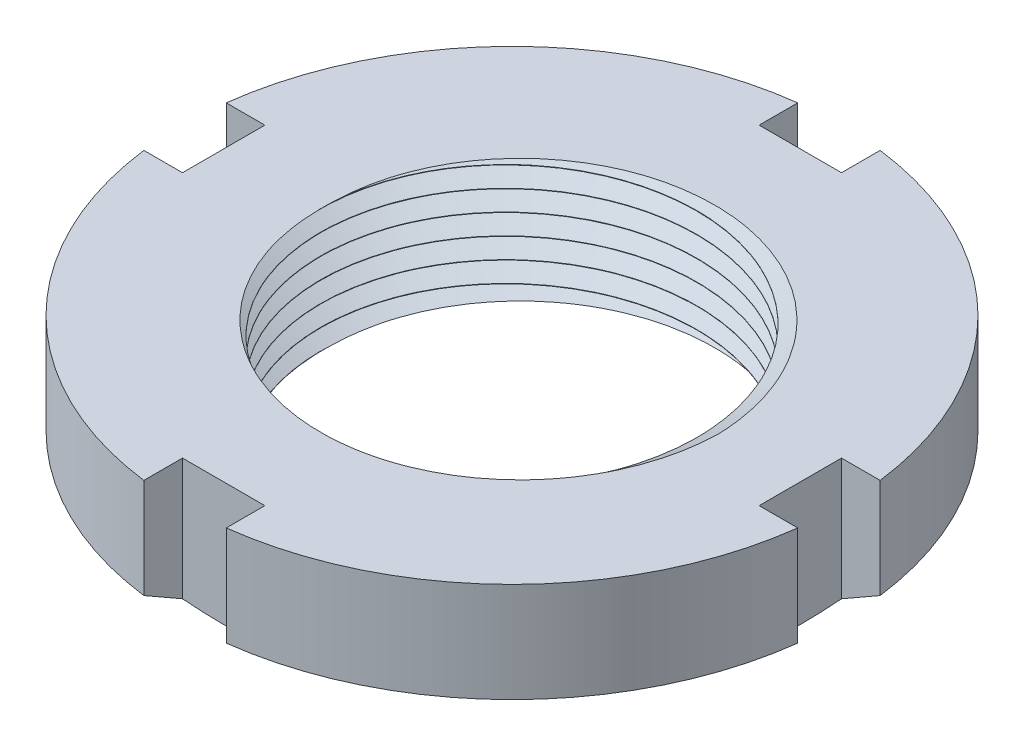
SolidWorks part; units mm, degrees
revolve "Base" add sketch "Esquisse1" angle 360 about L2
sketch "Esquisse1" plane through (0, 0, 0) normal (0, 0, 1) x (1, 0, 0)
  line L1 (9.134, 6) -> (16, 6)
  line L2 (0, 0) -> (0, 1.3) construction
  line L3 (16, 6) -> (16, 1.1547)
  line L4 (14, 0) -> (16, 1.1547)
  line L5 (14, 0) -> (9.134, 0)
  line L6 (-10, 0) -> (10, 0) construction
  line L7 (9.134, 0) -> (9.134, 6)
  line L8 (-16, 0) -> (16, 0) construction
  dimension "Hauteur" = 6
  dimension "D4" = 30
  dimension "D3" = 14
  dimension "Diamètre nominal" = 20
  dimension "Diamètre extérieur" = 32
  dimension "D6" = 9.134
  dimension "D1" = 16
ref_plane "Face" through (0, 0, 0) normal (0, 0, 1) x (1, 0, 0)
ref_plane "Dessus" through (0, 0, 0) normal (0, 1, 0) x (1, 0, 0)
ref_plane "Droite" through (0, 0, 0) normal (1, 0, 0) x (0, 0, -1)
ref_axis "Axe1" through (0, 6.8809, 0) along (0, -1, 0)
sketch "Esquisse2" plane through (0, 6, -4) normal (0, -1, 0) x (1, 0, 0)
  line L0 (0, -12) -> (0, 20) construction
  line L1 (16, 4) -> (-16, 4) construction
  line L2 (2, -12) -> (-2, -12)
  line L3 (2, -12) -> (2, -10)
  line L4 (2, -10) -> (-2, -10)
  line L5 (-2, -12) -> (-2, -10)
  line L6 (-2, 20) -> (-2, 18)
  line L7 (2, 18) -> (-2, 18)
  line L8 (2, 20) -> (2, 18)
  line L9 (2, 20) -> (-2, 20)
  line L10 (14, 6) -> (14, 2)
  line L11 (-16, 6) -> (-14, 6)
  line L12 (-16, 6) -> (-16, 2)
  line L13 (-16, 2) -> (-14, 2)
  line L14 (-14, 6) -> (-14, 2)
  line L15 (16, 2) -> (14, 2)
  line L16 (16, 6) -> (16, 2)
  line L17 (16, 6) -> (14, 6)
  circle A0 centre (0, 4) radius 16 construction
  dimension "D1" = 2
  dimension "D2" = 4
  dimension "D3" = 2
extrude "Encoches" cut sketch "Esquisse2" along normal through all
ref_plane "Plan filet" through (0, -1, 0) normal (0, 1, 0) x (-1, 0, 0)
sketch "Esquisse3" plane through (0, -1, -0.75) normal (0, 1, 0) x (1, 0, 0)
  circle A0 centre (0, -0.75) radius 10
  dimension "Diamètre nominal" = 20
sketch "Esquisse4" plane through (0, 0, 0) normal (0, 0, 1) x (1, 0, 0)
  line L0 (10, -1) -> (9.1209, -0.5027)
  line L1 (9.1209, -0.5027) -> (9.1209, -0.75)
  line L3 (10, -1) -> (8.6209, -1) construction
  line L4 (8.6209, -0.75) -> (8.6209, -1.25)
  line L5 (9.1209, -0.75) -> (8.6209, -0.75)
  line L6 (10, -1) -> (9.1209, -1.4973)
  line L7 (0, 0) -> (0, 3.4973) construction
  line L8 (9.3178, -1) -> (-9.3178, -1) construction
  line L9 (9.1209, -1.4973) -> (9.1209, -1.25)
  line L10 (9.1209, -1.25) -> (8.6209, -1.25)
  line L11 (9.1296, -0.5076) -> (9.1296, -1) construction
  line L12 (0, 0) -> (0, 1.3) construction
  dimension "Pas" = 1
  dimension "D1" = 1.01
  dimension "D5" = 0.5
  dimension "D3" = 10
  dimension "D2" = 29.5
curve "Hélice1" pitch 1 height 8 radius 10 centre (0, -1, 0) axis (0, 1, 0) start towards (1, 0, 0) parameters "Pas"=1
sweep "Filetage" cut profiles "Esquisse4" path "Hélice1" align with end faces yes
equation "\"D1@Esquisse1\" = \"Diamètre extérieur@Esquisse1\"/2"
equation "\"D6@Esquisse1\" = \"Diamètre nominal@Esquisse1\"/2-(\"Pas@Hélice1\"*sqr(3)/2)"
equation "\"D1@Esquisse2\" = \"Largeur fente@Esquisse2\"/2"
equation "\"D2@Esquisse2\" = \"Largeur fente@Esquisse2\""
equation "\"D3@Esquisse2\" = \"D2@Esquisse2\"/2"
equation "\"D3@Esquisse1\" = \"D1@Esquisse1\"-\"D3@Esquisse2\""
equation "\"D3@Hélice1\" = \"Hauteur@Esquisse1\"+(\"Pas@Hélice1\"*2)"
equation "\"D5@Hélice1\" = \"D3@Hélice1\"/\"Pas@Hélice1\""
equation "\"D1@Plan filet\" = \"Pas@Hélice1\""
equation "\"D5@Esquisse4\" = \"Pas@Esquisse4\"/2"
equation "\"D4@Esquisse4\" = \"Pas@Esquisse4\"/2"
equation "\"D1@Esquisse4\" = \"Pas@Esquisse4\"+(\"Pas@Esquisse4\"/100)"
equation "\"D3@Esquisse4\" = \"Diamètre nominal@Esquisse1\"/2"
